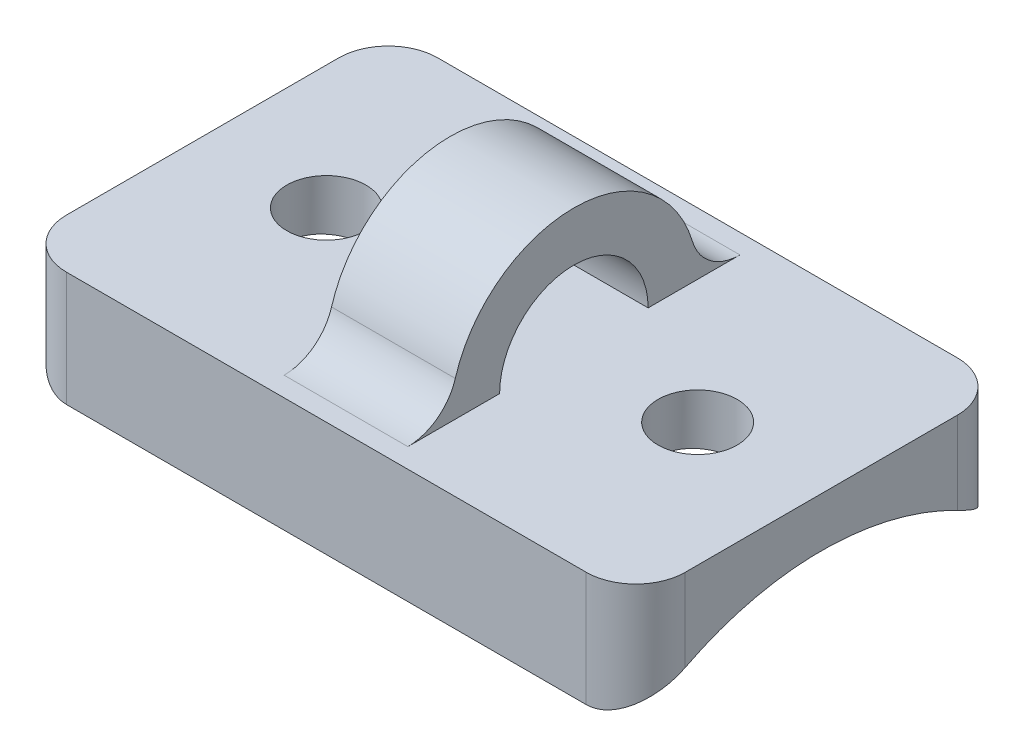
SolidWorks part; units mm, degrees
material "1060 Alloy"
ref_plane "Front Plane" through (0, 0, 0) normal (0, 0, 1) x (1, 0, 0)
ref_plane "Top Plane" through (0, 0, 0) normal (0, 1, 0) x (1, 0, 0)
ref_plane "Right Plane" through (0, 0, 0) normal (1, 0, 0) x (0, 0, -1)
sketch "Sketch1" plane through (0, 0, 0) normal (1, 0, 0) x (0, 0, -1)
  line L0 (7.5, 9.3675) -> (-7.5, 9.3675) construction
  line L1 (-7.5, 9.3675) -> (-7.5, 14)
  line L2 (-7.5, 14) -> (7.5, 14)
  line L3 (7.5, 14) -> (7.5, 9.3675)
  arc A0 (-7.5, 9.3675) -> (7.5, 9.3675) centre (0, 0) cw
  point P4 (0, 12)
  dimension "D1" = 12
  dimension "D3" = 2
  dimension "D2" = 7.5
extrude "Boss-Extrude1" add sketch "Sketch1" along normal mid plane 25
sketch "Sketch2" plane through (0, 0, 0) normal (1, 0, 0) x (0, 0, -1)
  line L0 (7.5, 14) -> (-7.5, 14) construction
  line L1 (0, 17) -> (0, 19) construction
  line L2 (-5, 14) -> (-3, 14)
  line L3 (3, 14) -> (5, 14)
  arc A0 (-5, 14) -> (5, 14) centre (0, 14) cw
  arc A1 (-3, 14) -> (3, 14) centre (0, 14) cw
  dimension "D1" = 5
  dimension "D2" = 2
extrude "Boss-Extrude2" add sketch "Sketch2" along normal mid plane 5
fillet "Fillet1" radius 2 6 edges at (12.5, 11.6837, -7.5) (-12.5, 11.6837, -7.5) (-12.5, 11.6837, 7.5) (12.5, 11.6837, 7.5) (0, 14, -5) (0, 14, 5)
sketch "Sketch3" plane through (0, 14, 0) normal (0, 1, 0) x (1, 0, 0)
  line L0 (-12.5, 0) -> (-7.5, 0) construction
  line L1 (-12.5, 5.5) -> (-12.5, -5.5) construction
  line L2 (12.5, 0) -> (7.5, 0) construction
  line L3 (12.5, 5.5) -> (12.5, -5.5) construction
  dimension "D1" = 5
hole_wizard "M3 Clearance Hole1" positions "Sketch4" profile "Sketch5" hole size "M3" standard "ANSI Metric" end condition through all
sketch "Sketch4" plane through (0, 14, 0) normal (0, 1, 0) x (1, 0, 0)
  point P0 (-7.5, 0)
  point P3 (7.5, 0)
sketch "Sketch5" plane through (-7.5, 14, 0) normal (1, 0, 0) x (0, 0, 1)
  line L0 (0, 0) -> (0, 4.8358)
  line L1 (0, 4.8358) -> (1.6, 4.8358)
  line L2 (1.6, 4.8358) -> (1.6, 0)
  line L5 (1.6, 0) -> (0, 0)
  line L11 (0, -6.35) -> (0, 107.95) construction
  dimension "Thru Hole Dia." = 3.2
  dimension "Thru Hole Depth" = 4.8358
equation "\"tubeOutDiameter\" = 35mm"
equation "\"wheelShaftDiameter\"= 12mm"
equation "\"wheelThickness\"= 135mm"
equation "\"BearingDiameter\"= 20mm"
equation "\"BearingThickness\"= 10mm"
equation "\"frontShaftDiameter\"= 20mm"
equation "\"D1@Sketch1\"=\"wheelShaftDiameter\""
